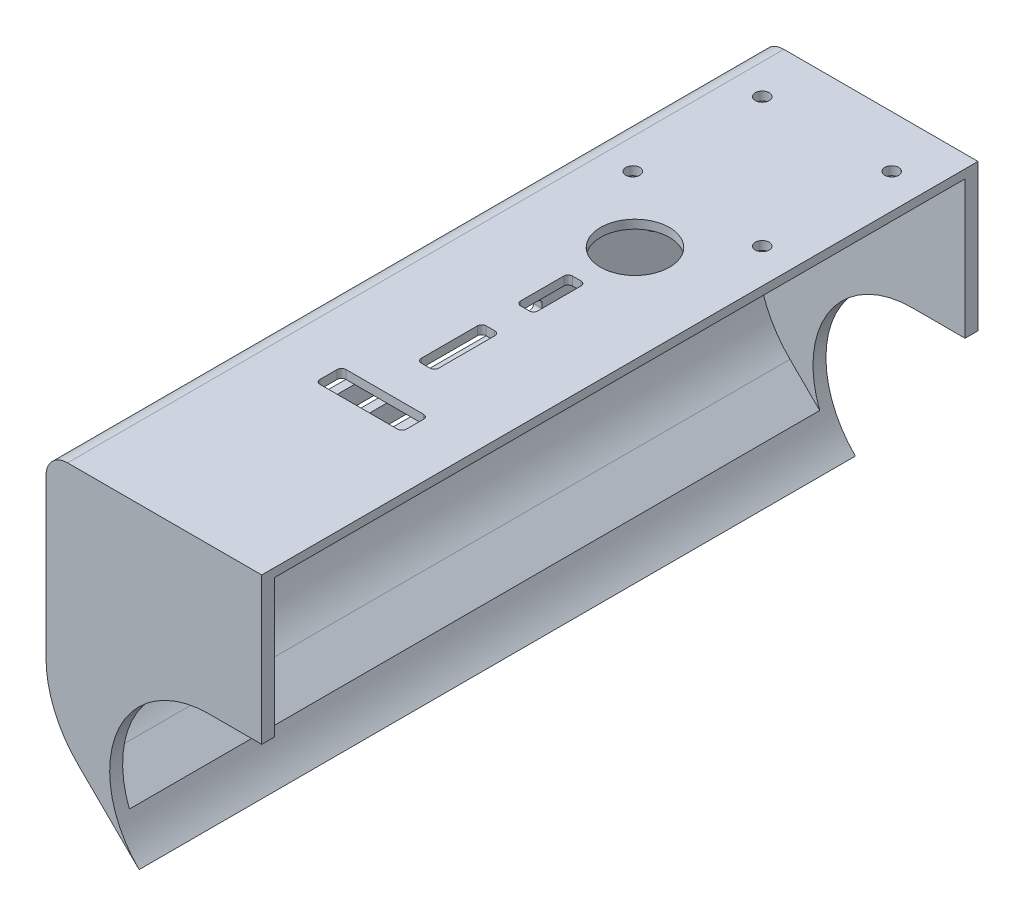
SolidWorks part; units mm, degrees
ref_plane "Front Plane" through (0, 0, 0) normal (0, 0, 1) x (1, 0, 0)
ref_plane "Top Plane" through (0, 0, 0) normal (0, 1, 0) x (1, 0, 0)
ref_plane "Right Plane" through (0, 0, 0) normal (1, 0, 0) x (0, 0, -1)
sketch "Sketch1" plane through (0, 0, 0) normal (0, 0, 1) x (1, 0, 0)
  line L0 (-176.4226, 3.6462) -> (-198.0073, 24.9918)
  line L1 (-198.0073, 24.9918) -> (-198.0073, 77)
  line L2 (-198.0073, 77) -> (-148.0073, 77)
  line L4 (-160.25, 43) -> (-148.0073, 43)
  line L6 (-148.0073, 43) -> (-148.0073, 77)
  arc A1 (-160.25, 43) -> (-176.4226, 3.6462) centre (-160.25, 20) ccw
extrude "Boss-Extrude1" add sketch "Sketch1" against normal blind 3
sketch "Sketch2" plane through (0, 0, -166) normal (0, 0, -1) x (-1, 0, 0)
  line L5 (198.0073, 24.9918) -> (198.0073, 77)
  line L6 (198.0073, 77) -> (148.0073, 77)
  line L7 (148.0073, 77) -> (148.0073, 43)
  line L8 (148.0073, 43) -> (160.25, 43)
  line L9 (176.4226, 3.6462) -> (198.0073, 24.9918)
  line L10 (198.0073, 24.9918) -> (198.0073, 77)
  line L11 (198.0073, 77) -> (148.0073, 77)
  line L12 (148.0073, 77) -> (148.0073, 43)
  line L13 (148.0073, 43) -> (160.25, 43)
  line L14 (176.4226, 3.6462) -> (198.0073, 24.9918)
  arc A1 (176.4226, 3.6462) -> (160.25, 43) centre (160.25, 20) ccw
  arc A2 (176.4226, 3.6462) -> (160.25, 43) centre (160.25, 20) ccw
  dimension "D1" = 0
extrude "Boss-Extrude2" add sketch "Sketch2" against normal blind 3 separate body
sketch "Sketch3" plane through (0, 0, -3) normal (0, 0, -1) x (-1, 0, 0)
  line L0 (181.6864, 11.6645) -> (196.0073, 25.8268)
  line L1 (196.0073, 25.8268) -> (196.0073, 75)
  line L2 (196.0073, 75) -> (148.0073, 75)
  line L3 (148.0073, 77) -> (148.0073, 75)
  line L4 (175.0163, 5.0683) -> (196.0073, 25.8268) construction
  line L5 (198.0073, 24.9918) -> (198.0073, 77)
  line L6 (198.0073, 77) -> (148.0073, 77)
  line L7 (148.0073, 77) -> (148.0073, 43)
  line L8 (148.0073, 43) -> (160.25, 43)
  line L9 (176.4226, 3.6462) -> (198.0073, 24.9918)
  line L10 (198.0073, 24.9918) -> (198.0073, 77)
  line L11 (198.0073, 77) -> (148.0073, 77)
  line L14 (176.4226, 3.6462) -> (198.0073, 24.9918)
  arc A0 (160.25, -3) -> (160.25, 43) centre (160.25, 20) ccw construction
  arc A1 (176.4226, 3.6462) -> (160.25, 43) centre (160.25, 20) ccw
  arc A3 (176.4226, 3.6462) -> (181.6864, 11.6645) centre (160.25, 20) ccw
  dimension "D1" = 0
  dimension "D2" = 2
extrude "Boss-Extrude3" add sketch "Sketch3" along normal up to surface (160 mm away) up to face at (-173.6482, 45.6762, -163)
fillet "Fillet1" radius 5 2 edges at (-198.0073, 77, -83) (-196.0073, 75, -83)
fillet "Fillet2" radius 25 2 edges at (-196.0073, 25.8268, -83) (-198.0073, 24.9918, -83)
sketch "Sketch4" plane through (-198.0073, 0, 0) normal (-1, 0, 0) x (0, 0, 1)
  line L0 (-83, 77) -> (-83, 3.6462) construction
  line L1 (-166, 77) -> (0, 77) construction
  line L2 (-166, 3.6462) -> (0, 3.6462) construction
  line L3 (-112, 59.5) -> (-54, 59.5)
  line L4 (-112, 67) -> (-54, 67)
  line L5 (-113, 66) -> (-113, 65)
  line L6 (-112, 64) -> (-54, 64)
  line L7 (-53, 66) -> (-53, 65)
  line L8 (-113, 58.5) -> (-113, 57.5)
  line L9 (-112, 56.5) -> (-54, 56.5)
  line L10 (-53, 58.5) -> (-53, 57.5)
  line L11 (-112, 52) -> (-54, 52)
  line L12 (-113, 51) -> (-113, 50)
  line L13 (-112, 49) -> (-54, 49)
  line L14 (-53, 51) -> (-53, 50)
  line L15 (-112, 44.5) -> (-54, 44.5)
  line L16 (-113, 43.5) -> (-113, 42.5)
  line L17 (-112, 41.5) -> (-54, 41.5)
  line L18 (-53, 43.5) -> (-53, 42.5)
  arc A0 (-54, 67) -> (-53, 66) centre (-54, 66) cw
  arc A1 (-54, 64) -> (-53, 65) centre (-54, 65) ccw
  arc A2 (-112, 67) -> (-113, 66) centre (-112, 66) ccw
  arc A3 (-113, 65) -> (-112, 64) centre (-112, 65) ccw
  arc A4 (-54, 59.5) -> (-53, 58.5) centre (-54, 58.5) cw
  arc A5 (-54, 56.5) -> (-53, 57.5) centre (-54, 57.5) ccw
  arc A6 (-112, 59.5) -> (-113, 58.5) centre (-112, 58.5) ccw
  arc A7 (-113, 57.5) -> (-112, 56.5) centre (-112, 57.5) ccw
  arc A8 (-54, 52) -> (-53, 51) centre (-54, 51) cw
  arc A9 (-54, 49) -> (-53, 50) centre (-54, 50) ccw
  arc A10 (-112, 52) -> (-113, 51) centre (-112, 51) ccw
  arc A11 (-113, 50) -> (-112, 49) centre (-112, 50) ccw
  arc A12 (-54, 44.5) -> (-53, 43.5) centre (-54, 43.5) cw
  arc A13 (-54, 41.5) -> (-53, 42.5) centre (-54, 42.5) ccw
  arc A14 (-112, 44.5) -> (-113, 43.5) centre (-112, 43.5) ccw
  arc A15 (-113, 42.5) -> (-112, 41.5) centre (-112, 42.5) ccw
  dimension "D1" = 1
  dimension "D2" = 4
extrude "Cut-Extrude1" cut sketch "Sketch4" against normal blind 5
sketch "Sketch5" plane through (0, 77, 0) normal (0, 1, 0) x (1, 0, 0)
  line L1 (-180.5073, 51) -> (-160.5073, 51)
  line L2 (-180.5073, 51) -> (-180.5073, 45)
  line L3 (-180.5073, 45) -> (-160.5073, 45)
  line L4 (-160.5073, 51) -> (-160.5073, 45)
  line L5 (-173.0073, 76) -> (-169.0073, 76)
  line L6 (-173.0073, 76) -> (-173.0073, 61)
  line L7 (-173.0073, 61) -> (-169.0073, 61)
  line L8 (-169.0073, 76) -> (-169.0073, 61)
  line L9 (-173.0073, 96) -> (-169.0073, 96)
  line L10 (-173.0073, 96) -> (-173.0073, 84)
  line L11 (-173.0073, 84) -> (-169.0073, 84)
  line L12 (-169.0073, 96) -> (-169.0073, 84)
  line L13 (-148.0073, 0) -> (-193.0073, 0) construction
  line L14 (-170.5073, 0) -> (-170.5073, 45) construction
  circle A0 centre (-170.5073, 109) radius 8
extrude "Cut-Extrude2" cut sketch "Sketch5" against normal blind 2
sketch "Sketch6" plane through (0, 77, 0) normal (0, 1, 0) x (1, 0, 0)
  circle A0 centre (-156.0073, 154) radius 1.6
  circle A1 centre (-156.0073, 124) radius 1.6
  circle A2 centre (-186.0073, 124) radius 1.6
  circle A3 centre (-186.0073, 154) radius 1.6
extrude "Cut-Extrude3" cut sketch "Sketch6" against normal up to surface (2 mm away) up to face at (-170.5073, 75, -48)
fillet "Fillet3" radius 1 12 edges at (-169.0073, 76, -76) (-173.0073, 76, -76) (-169.0073, 76, -84) (-173.0073, 76, -84) (-173.0073, 76, -96) (-169.0073, 76, -96) (-160.5073, 76, -45) (-160.5073, 76, -51) (-180.5073, 76, -51) (-180.5073, 76, -45) (-173.0073, 76, -61) (-169.0073, 76, -61)
sketch "Sketch7" plane through (-198.0073, 0, 0) normal (-1, 0, 0) x (0, 0, 1)
  circle A0 centre (-141, 57) radius 5
extrude "Cut-Extrude4" cut sketch "Sketch7" against normal blind 3
